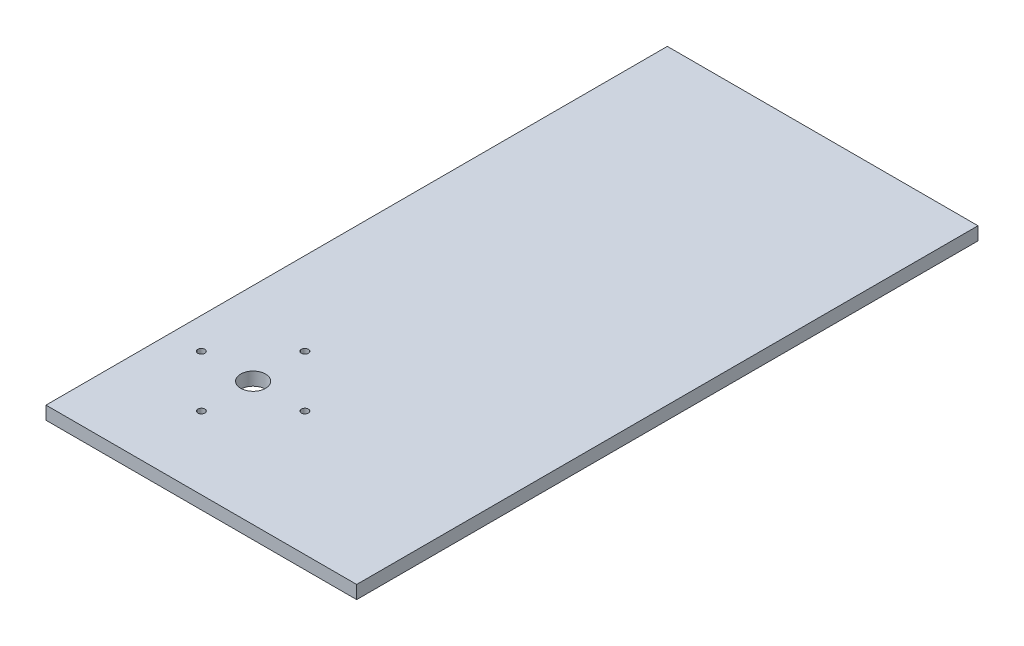
SolidWorks part; units mm, degrees
ref_plane "Front Plane" through (0, 0, 0) normal (0, 0, 1) x (1, 0, 0)
ref_plane "Top Plane" through (0, 0, 0) normal (0, 1, 0) x (1, 0, 0)
ref_plane "Right Plane" through (0, 0, 0) normal (1, 0, 0) x (0, 0, -1)
sketch "Sketch1" plane through (0, 0, 0) normal (0, 1, 0) x (1, 0, 0)
  line L1 (-75, -150) -> (75, -150)
  line L2 (-75, -150) -> (-75, 150)
  line L3 (-75, 150) -> (75, 150)
  line L4 (75, -150) -> (75, 150)
  line L5 (-75, -150) -> (75, 150) construction
  line L6 (-75, 150) -> (75, -150) construction
  point P0 (0, 0)
  dimension "D1" = 300
  dimension "D2" = 150
extrude "Boss-Extrude1" add sketch "Sketch1" along normal blind 6.35
sketch "Sketch2" plane through (0, 6.35, 0) normal (0, 1, 0) x (1, 0, 0)
  line L0 (-35, -150) -> (-35, 150) construction
  line L1 (-75, -150) -> (75, -150) construction
  line L2 (75, 150) -> (-75, 150) construction
  line L3 (-35, -115) -> (-35, -65) construction
  line L4 (-60, -90) -> (-10, -90) construction
  line L5 (-75, 150) -> (-75, -150) construction
  circle A0 centre (-35, -90) radius 6
  circle A1 centre (-35, -65) radius 1.7
  circle A2 centre (-10, -90) radius 1.7
  circle A3 centre (-35, -115) radius 1.7
  circle A4 centre (-60, -90) radius 1.7
  point P11 (-35, -90)
  point P14 (-35, -90)
  dimension "D1" = 12
  dimension "D4" = 60
  dimension "D6" = 3.4
  dimension "D2" = 50
  dimension "D3" = 50
  dimension "D5" = 40
extrude "Cut-Extrude1" cut sketch "Sketch2" against normal through all
